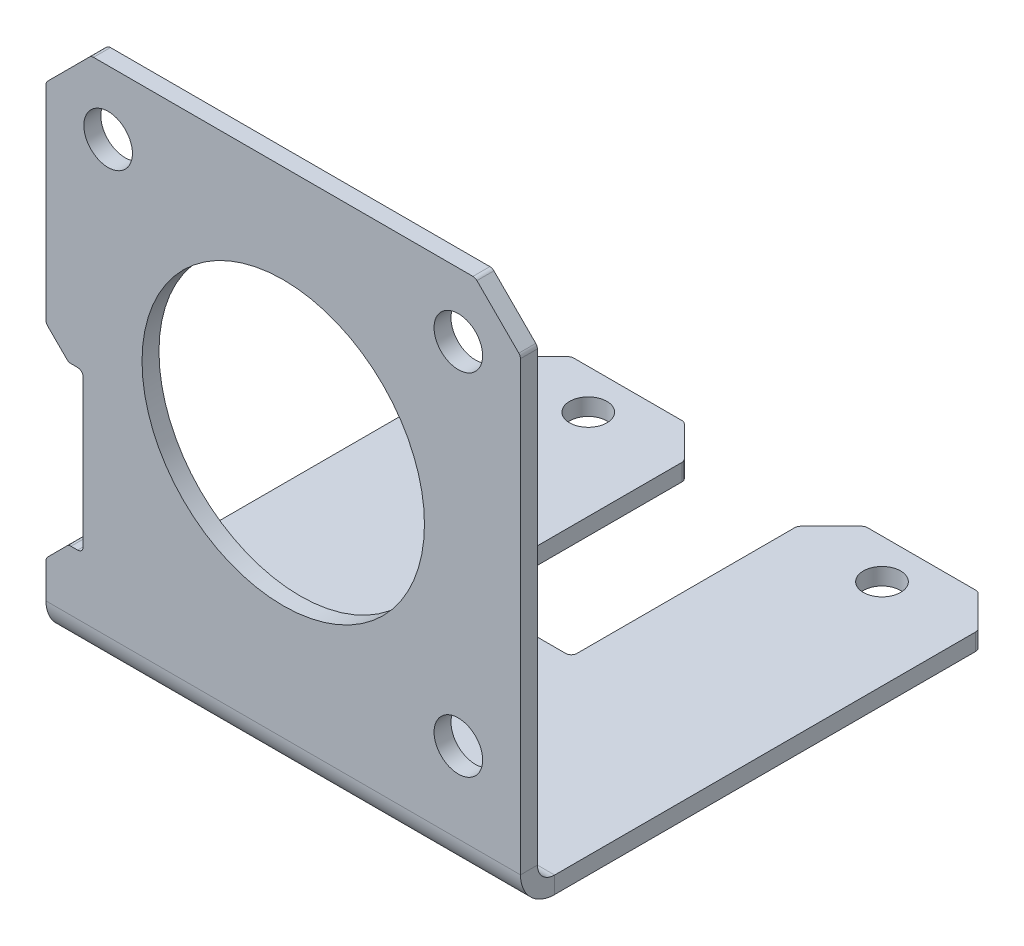
SolidWorks part; units mm, degrees
note: The reader was unsure of these and kept them because the rebuilt part matched: thickness of "Base-Flange1", "Edge-Flange1", "Sheet-Metal(1)", "Sheet-Metal(2)", "Sheet-Metal(3)", "Sheet-Metal(4)", "Sheet-Metal(12)", "Sheet-Metal(19)", "Sheet-Metal(20)"; flange length of "Edge-Flange1".
material "AISI 1020 Steel, Cold Rolled"
ref_plane "Front" through (0, 0, 0) normal (0, 0, 1) x (1, 0, 0)
ref_plane "Top" through (0, 0, 0) normal (0, 1, 0) x (1, 0, 0)
ref_plane "Right" through (0, 0, 0) normal (1, 0, 0) x (0, 0, -1)
sketch "Sketch1" plane through (0, 0, 0) normal (0, 1, 0) x (1, 0, 0)
  line L0 (0, 0) -> (0, 43.9909) construction
  line L1 (-21, 43.5) -> (-5, 43.5)
  line L2 (-5, 43.5) -> (-5, 20.5)
  line L3 (-5, 20.5) -> (5, 20.5)
  line L4 (5, 20.5) -> (5, 43.5)
  line L5 (5, 43.5) -> (21, 43.5)
  line L6 (21, 43.5) -> (21, 0)
  line L7 (21, 0) -> (-21, 0)
  line L8 (-21, 0) -> (-21, 43.5)
  dimension "D1" = 10
  dimension "D2" = 42
  dimension "D3" = 20.5
  dimension "D4" = 43.5
base flange "Base-Flange1" sketch "Sketch1" thickness 1.5 reverse thickness direction no parameters "D1"=1.524
edge flange "Edge-Flange1" sketch "Sketch8" flange angle 90 flange length 45.3 flange position material inside bend radius 1.524 thickness 1.5 relief rectangular parameters "D6"=10
sketch "Sketch8" plane through (0, 0, 0) normal (0, 0, 1) x (1, 0, 0)
  line L0 (-21, 0) -> (21, 0) construction
  line L1 (-21, 0) -> (21, 0)
  line L2 (-21, 0) -> (-21, 45.3)
  line L3 (-21, 45.3) -> (21, 45.3)
  line L4 (21, 45.3) -> (21, 0)
bend "EdgeBend1" bend radius 1.524 bend angle 90 parameters "D5"=1
sketch "Sketch9" plane through (0, 0, 0) normal (0, 0, 1) x (1, 0, 0)
  line L0 (0, 45.3) -> (0, -5.7392) construction
  line L1 (21, 45.3) -> (-21, 45.3) construction
  line L2 (-21, 24.15) -> (33.2708, 24.15) construction
  line L3 (-21, 45.3) -> (-21, 1.524) construction
  circle A0 centre (0, 24.15) radius 12.5
  dimension "D2" = 25
  dimension "D1" = 21.15
extrude "Cut-Extrude1" cut sketch "Sketch9" against normal up to surface (1.5 mm away) normal cut yes up to face at (0, 23.412, -1.5)
sketch "Sketch10" plane through (0, 0, 0) normal (0, 0, 1) x (1, 0, 0)
  line L0 (0, 24.15) -> (38.4566, 24.15) construction
  line L1 (0, 24.15) -> (0, 37.616) construction
  circle A0 centre (-15.5, 39.65) radius 2.15
  circle A1 centre (15.5, 39.65) radius 2.15
  circle A2 centre (15.5, 8.65) radius 2.15
  circle A4 centre (0, 24.15) radius 12.5 construction
  dimension "D3" = 31
  dimension "D2" = 4.3
  dimension "D1" = 31
extrude "Cut-Extrude2" cut sketch "Sketch10" against normal through all normal cut yes
sketch "Sketch11" plane through (0, 0, 0) normal (0, 1, 0) x (1, 0, 0)
  line L0 (0, 29.2687) -> (0, 9.8529) construction
  line L1 (0, -50) -> (0, 50) construction
  line L2 (-50, 0) -> (50, 0) construction
  line L3 (-5, 20.5) -> (-5, 43.5) construction
  line L4 (-21, 43.5) -> (-21, 3.024) construction
  circle A0 centre (-13, 40) radius 1.65
  circle A1 centre (13, 40) radius 1.65
  dimension "D1" = 26
  dimension "D2" = 40
  dimension "D3" = 3.3
  dimension "D4" = 8
  dimension "D5" = 8
extrude "Cut-Extrude3" cut sketch "Sketch11" against normal through all normal cut yes
chamfer "Chamfer1" distance 4 angle 45 2 edges at (21, 45.3, -0.75) (-21, 45.3, -0.75)
chamfer "Chamfer2" distance 3 angle 45 4 edges at (-5, -0.75, -43.5) (-21, -0.75, -43.5) (21, -0.75, -43.5) (5, -0.75, -43.5)
sketch "Sketch12" plane through (0, 0, 0) normal (0, 0, 1) x (1, 0, 0)
  line L0 (-21, 41.3) -> (-21, 1.524) construction
  line L1 (-21, 20.8191) -> (-17.704, 20.8191)
  line L2 (-21, 20.8191) -> (-21, 6.8191)
  line L3 (-21, 6.8191) -> (-17.704, 6.8191)
  line L4 (-17.704, 20.8191) -> (-17.704, 6.8191)
  line L5 (21, -1.5) -> (-21, -1.5) construction
  dimension "D1" = 8.3191
  dimension "D2" = 14
  dimension "D3" = 3.296
extrude "Cut-Extrude4" cut sketch "Sketch12" against normal through all normal cut yes
chamfer "Chamfer3" distance 2 angle 45 2 edges at (-21, 6.8191, -0.75) (-21, 20.8191, -0.75)
sketch "Sketch13" plane through (0, 0, 0) normal (0, 1, 0) x (1, 0, 0)
  line L0 (5, 20.5) -> (-5, 20.5) construction
  circle A0 centre (0, 17.25) radius 1.25
  point P2 (0, 20.5)
  dimension "D2" = 2.5
  dimension "D1" = 3.25
extrude "Cut-Extrude5" cut sketch "Sketch13" against normal through all normal cut yes
fillet "Fillet1" radius 0.5 20 edges at (-17.704, 6.8191, -0.75) (-17.704, 20.8191, -0.75) (-19, 6.8191, -0.75) (-21, 4.8191, -0.75) (-19, 20.8191, -0.75) (-21, 22.8191, -0.75) (-21, 41.3, -0.75) (-17, 45.3, -0.75) (17, 45.3, -0.75) (21, 41.3, -0.75) (-21, -0.75, -40.5) (-18, -0.75, -43.5) (-8, -0.75, -43.5) (5, -0.75, -20.5) (-5, -0.75, -20.5) (-5, -0.75, -40.5) (5, -0.75, -40.5) (8, -0.75, -43.5) (18, -0.75, -43.5) (21, -0.75, -40.5)
sketch "Bend-Lines1" [suppressed] plane through (0, 0, 0) normal (0, 1, 0) x (1, 0, 0)
sketch "Bounding-Box1" [suppressed] plane through (0, 0, 0) normal (0, 1, 0) x (1, 0, 0)
sheet metal parameters "Sheet-Metal(1)" thickness 1.5 parameters "D1"=1.524
flat pattern "Flat-Pattern(1)" [suppressed]
sketch "Bend-Lines2" plane through (0, 0, 0) normal (0, 1, 0) x (1, 0, 0)
sketch "Bounding-Box2" [suppressed] plane through (0, 0, 0) normal (0, 1, 0) x (1, 0, 0)
sheet metal parameters "Sheet-Metal(2)" thickness 1.5 parameters "D1"=1.524, "D7"=2
flat pattern "Flat-Pattern(1)" [suppressed]
sketch "Bend-Lines2" plane through (0, 0, 0) normal (0, 1, 0) x (1, 0, 0)
sketch "Bounding-Box2" [suppressed] plane through (0, 0, 0) normal (0, 1, 0) x (1, 0, 0)
bend of the flat pattern "Flatten-<EdgeBend1>1"
sheet metal parameters "Sheet-Metal(3)" thickness 1.5 parameters "D1"=1.524, "D7"=2
flat pattern "Flat-Pattern(1)" [suppressed]
sketch "Bend-Lines2" plane through (0, 0, 0) normal (0, 1, 0) x (1, 0, 0)
sketch "Bounding-Box2" [suppressed] plane through (0, 0, 0) normal (0, 1, 0) x (1, 0, 0)
bend of the flat pattern "Flatten-<EdgeBend1>1"
sheet metal parameters "Sheet-Metal(4)" thickness 1.5 parameters "D1"=1.524, "D7"=2
flat pattern "Flat-Pattern(1)" [suppressed]
sketch "Bend-Lines2" plane through (0, 0, 0) normal (0, 1, 0) x (1, 0, 0)
sketch "Bounding-Box2" [suppressed] plane through (0, 0, 0) normal (0, 1, 0) x (1, 0, 0)
bend of the flat pattern "Flatten-<EdgeBend1>1"
sheet metal parameters "Sheet-Metal(12)" thickness 1.5 parameters "D1"=1.524, "D7"=2
flat pattern "Flat-Pattern(1)"
sketch "Bend-Lines2" plane through (0, 0, 0) normal (0, 1, 0) x (1, 0, 0)
  line L0 (-21, 2.262) -> (21, 2.262) construction
  line L1 (-21, 2.262) -> (21, 2.262) construction
sketch3d "Bounding-Box2" [suppressed]
  line L0 (-21, -42.276, 0) -> (-21, 43.5, 0) construction
  line L1 (21, -42.276, 0) -> (21, 43.5, 0) construction
  line L2 (-21, -42.276, 0) -> (21, -42.276, 0) construction
  line L3 (-21, 43.5, 0) -> (21, 43.5, 0) construction
bend of the flat pattern "Flatten-<EdgeBend1>1"
sheet metal parameters "Sheet-Metal(19)" thickness 1.5 parameters "D1"=1.524, "D7"=2
flat pattern "Flat-Pattern(1)"
sketch "Bend-Lines2" plane through (0, 0, 0) normal (0, 1, 0) x (1, 0, 0)
  line L0 (-21, 2.262) -> (21, 2.262) construction
  line L1 (-21, 2.262) -> (21, 2.262) construction
sketch3d "Bounding-Box2" [suppressed]
  line L0 (-21, -42.276, 0) -> (-21, 43.5, 0) construction
  line L1 (21, -42.276, 0) -> (21, 43.5, 0) construction
  line L2 (-21, -42.276, 0) -> (21, -42.276, 0) construction
  line L3 (-21, 43.5, 0) -> (21, 43.5, 0) construction
bend of the flat pattern "Flatten-<EdgeBend1>1"
sheet metal parameters "Sheet-Metal(20)" thickness 1.5 parameters "D1"=1.524, "D7"=2
flat pattern "Flat-Pattern(1)"
sketch "Bend-Lines2" plane through (0, 0, 0) normal (0, 1, 0) x (1, 0, 0)
  line L0 (-21, 2.262) -> (21, 2.262) construction
  line L1 (-21, 2.262) -> (21, 2.262) construction
sketch3d "Bounding-Box2" [suppressed]
  line L0 (-21, -42.276, 0) -> (-21, 43.5, 0) construction
  line L1 (21, -42.276, 0) -> (21, 43.5, 0) construction
  line L2 (-21, -42.276, 0) -> (21, -42.276, 0) construction
  line L3 (-21, 43.5, 0) -> (21, 43.5, 0) construction
bend of the flat pattern "Flatten-<EdgeBend1>1"
